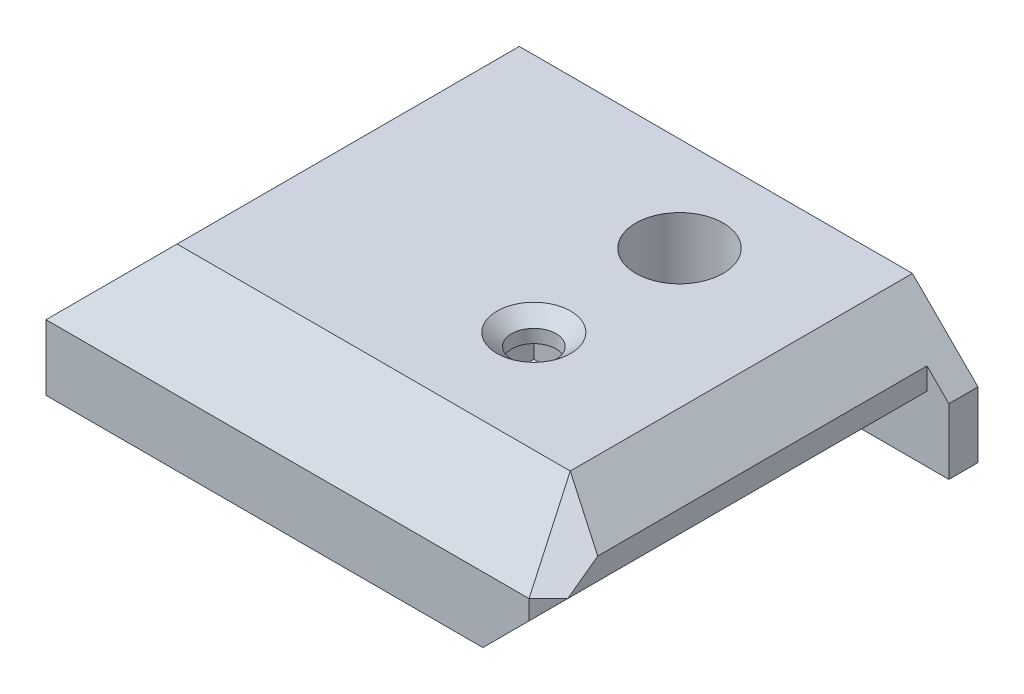
SolidWorks part; units mm, degrees
ref_plane "Front Plane" through (0, 0, 0) normal (0, 0, 1) x (1, 0, 0)
ref_plane "Top Plane" through (0, 0, 0) normal (0, 1, 0) x (1, 0, 0)
ref_plane "Right Plane" through (0, 0, 0) normal (1, 0, 0) x (0, 0, -1)
sketch "Sketch1" plane through (0, 0, 0) normal (0, 0, 1) x (1, 0, 0)
  line L0 (0, 0) -> (0, 9)
  line L1 (0, 9) -> (36, 9)
  line L2 (36, 9) -> (36, 0)
  line L3 (55, 0) -> (-55, 0) construction
  line L4 (36, 0) -> (0, 0)
extrude "Boss-Extrude1" add sketch "Sketch1" along normal blind 28
ref_plane "Plane1" through (0, 4.5, 0) normal (0, -1, 0) x (-1, 0, 0)
sketch "Sketch2" plane through (0, 0, 0) normal (0, 0, 1) x (1, 0, 0)
  line L0 (0, 4.5) -> (4.5, 9)
  line L1 (0, 9) -> (0, 0) construction
  line L2 (36, 9) -> (0, 9) construction
  line L3 (0, 4.5) -> (0, 9)
  line L4 (0, 9) -> (4.5, 9)
  line L5 (18, 10.7859) -> (18, -2.0026) construction
  line L6 (36, 4.5) -> (31.5, 9)
  line L7 (36, 4.5) -> (36, 9)
  line L8 (36, 9) -> (31.5, 9)
extrude "Cut-Extrude1" cut sketch "Sketch2" along normal blind 28
sketch "Sketch3" plane through (0, 0, 0) normal (1, 0, 0) x (0, 0, -1)
  line L0 (-28, 4.5) -> (-23.5, 9)
  line L1 (-28, 4.5) -> (0, 4.5) construction
  line L2 (-28, 0) -> (-28, 4.5) construction
  line L3 (-28, 9) -> (0, 9) construction
  line L4 (-28, 4.5) -> (-28, 9)
  line L5 (-28, 9) -> (-23.5, 9)
extrude "Cut-Extrude2" cut sketch "Sketch3" along normal blind 36
ref_plane "Plane2" through (32, 0, 32) normal (0.7071, 0, 0.7071) x (0, 1, 0)
sketch "Sketch5" plane through (32, 0, 32) normal (0.7071, 0, 0.7071) x (0, 1, 0)
  line L0 (0, -15.4) -> (0, 15.4) construction
  line L1 (0, 1.8738) -> (11.4404, 1.8738)
  line L2 (0, 1.8738) -> (0, -13.7452)
  line L3 (0, -13.7452) -> (11.4404, -13.7452)
  line L4 (11.4404, 1.8738) -> (11.4404, -13.7452)
extrude "Cut-Extrude4" cut sketch "Sketch5" against normal blind 2
ref_plane "Plane3" through (4, 0, -4) normal (-0.7071, 0, 0.7071) x (0.5774, -0.5774, 0.5774)
sketch "Sketch6" plane through (4, 0, -4) normal (-0.7071, 0, 0.7071) x (0.5774, -0.5774, 0.5774)
  line L0 (26.5581, 29.8021) -> (32.7193, 28.6474)
  line L1 (32.7193, 28.6474) -> (30.1986, 32.2123)
  line L2 (30.1986, 32.2123) -> (26.5581, 29.8021)
extrude "Cut-Extrude5" cut sketch "Sketch6" against normal blind 2 and the other way blind 2
sketch "Sketch7" plane through (0, 0, 0) normal (0, 0, 1) x (1, 0, 0)
  line L0 (0, 0) -> (5, 0) construction
  line L1 (15.4226, 0) -> (-15.4226, 0) construction
  line L2 (5, 0) -> (5, 3)
  line L3 (5, 0) -> (13.8116, 0)
  line L4 (13.8116, 0) -> (13.8116, 3)
  line L5 (5, 3) -> (5.7071, 3.7071)
  line L9 (13.8116, 3) -> (13.1045, 3.7071)
  line L10 (5.7071, 3.7071) -> (13.1045, 3.7071)
extrude "Cut-Extrude6" cut sketch "Sketch7" along normal blind 26
ref_plane "Plane5" through (0, 0, 28) normal (0, 0, 1) x (1, 0, 0)
sketch "Sketch8" plane through (0, 0, 28) normal (0, 0, 1) x (1, 0, 0)
  line L1 (15.4, 0) -> (-15.4, 0) construction
  line L2 (36, 0) -> (36, 4.5) construction
  line L3 (36, 0) -> (30, 0)
  line L5 (31.5, 9) -> (36, 4.5) construction
  line L8 (34.5, 4.5) -> (34.5, 6)
  line L9 (33.1716, 4.5) -> (36, 4.5) construction
  line L10 (34.5, 6) -> (36, 6)
  line L11 (36, 6) -> (36, 0)
  line L12 (34.5, 4.5) -> (30, 0)
  point P1 (0, 0)
  point P9 (0, 0)
  point P16 (0, 0)
  point P18 (35.9143, 0.7425)
  point P19 (36.0398, 0)
extrude "Cut-Extrude7" cut sketch "Sketch8" against normal blind 26
sketch "Sketch9" plane through (0, 0, 0) normal (0, 1, 0) x (1, 0, 0)
  line L0 (0, -6.5) -> (19, -6.5) construction
  line L1 (0, -4.95) -> (0, 4.95) construction
  line L2 (5.7775, 0) -> (5.7775, -6.5) construction
  line L3 (-6.8862, 0) -> (6.8862, 0) construction
  line L4 (19, -6.5) -> (22, -6.5)
  circle A0 centre (22, -6.5) radius 3
sketch "Sketch10" plane through (0, 9, 0) normal (0, 1, 0) x (1, 0, 0)
  circle A0 centre (22, -6.5) radius 3
extrude "Cut-Extrude8" cut sketch "Sketch10" against normal blind 7
sketch "Sketch11" plane through (0, 2, 0) normal (0, 1, 0) x (1, 0, 0)
  circle A0 centre (22, -6.5) radius 1.5
extrude "Cut-Extrude9" cut sketch "Sketch11" against normal up to surface (2 mm away) up to face at (16.9623, 0, 11.2)
sketch "Sketch12" plane through (0, 0, 0) normal (0, 1, 0) x (1, 0, 0)
  line L0 (22, -8) -> (22, -15) construction
  line L1 (22, -15) -> (22, -16.5)
  circle A0 centre (22, -6.5) radius 1.5 construction
  circle A1 centre (22, -16.5) radius 1.5
extrude "Cut-Extrude10" cut sketch "Sketch12" along normal up to surface (9 mm away) contours A1 region at (20.9693, 0, 17.5307) up to face at (22, 9, 9.5)
hole_wizard "CSK for #3 Flat Head Machine Screw (100)1" positions "3DSketch1" profile "Sketch13" countersink size "#3" standard "ANSI Inch" end condition up to next
sketch3d "3DSketch1"
  line L0 (22, 9, 16.5) -> (22, 0, 16.5) construction
  point P0 (22, 9, 16.5)
sketch "Sketch13" plane through (22, 9, 16.5) normal (1, 0, 0) x (0, 0, 1)
  line L0 (0, 0) -> (0, 9)
  line L1 (0, 9) -> (1.524, 9)
  line L2 (1.524, 9) -> (1.524, 0.8419)
  line L3 (1.524, 0.8419) -> (2.5273, 0)
  line L5 (2.5273, 0) -> (0, 0)
  line L6 (-1.524, 0.8419) -> (-2.5273, 0) construction
  line L11 (0, -6.35) -> (0, 107.95) construction
  dimension "Thru Hole Dia." = 3.048
  dimension "Thru Hole Depth" = 9
  dimension "Near C'Sink Dia." = 5.0546
  dimension "Near C'Sink Angle" = 100
ref_plane "Plane6" through (0, 4.75, 0) normal (0, 1, 0) x (1, 0, 0)
sketch "Sketch15" plane through (0, 4.75, 0) normal (0, 1, 0) x (1, 0, 0)
  line L0 (22, -16.5) -> (22, -13.85) construction
  line L1 (22, -16.5) -> (19.35, -16.5) construction
  line L2 (20.576, -1.325) -> (20.576, 1.325) construction
  line L3 (22, -16.5) -> (24.65, -16.5) construction
  line L4 (22, -19.15) -> (22, -16.5) construction
  line L6 (19.35, -19.15) -> (24.65, -19.15)
  line L7 (19.35, -19.15) -> (19.35, -13.85)
  line L8 (19.35, -13.85) -> (24.65, -13.85)
  line L9 (24.65, -19.15) -> (24.65, -13.85)
extrude "Cut-Extrude11" cut sketch "Sketch15" along normal blind 2.5
